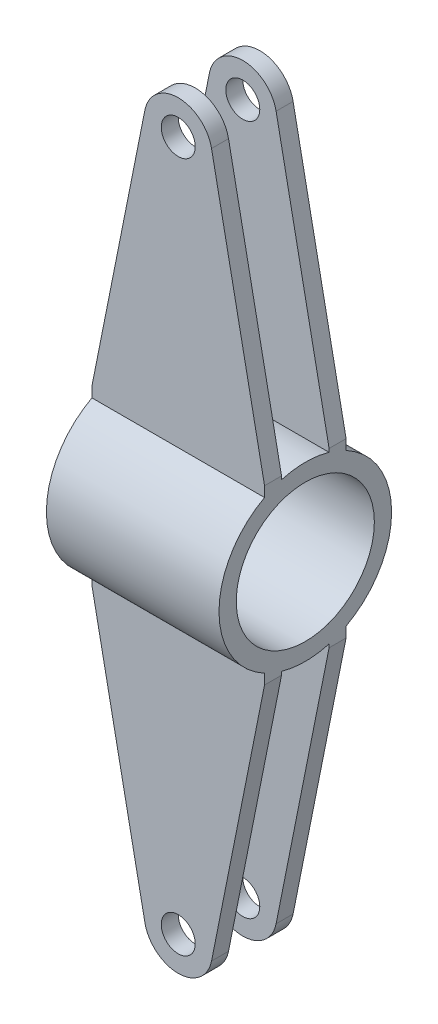
SolidWorks part; units mm, degrees
ref_plane "Front Plane" through (0, 0, 0) normal (0, 0, 1) x (1, 0, 0)
ref_plane "Top Plane" through (0, 0, 0) normal (0, 1, 0) x (1, 0, 0)
ref_plane "Right Plane" through (0, 0, 0) normal (1, 0, 0) x (0, 0, -1)
sketch "Sketch1" plane through (0, 0, 0) normal (0, 0, 1) x (1, 0, 0)
  line L0 (0, 101.6) -> (0, -101.6) construction
  point P4 (0, 0)
  dimension "D1" = 203.2
sketch "Sketch3" plane through (0, 0, 0) normal (1, 0, 0) x (0, 0, -1)
  circle A0 centre (0, 0) radius 25.4
  circle A1 centre (0, 0) radius 20.32
  dimension "D1" = 50.8
  dimension "D2" = 5.08
extrude "Boss-Extrude1" add sketch "Sketch3" along normal mid plane 50.8
sketch "Sketch4" plane through (0, 0, 0) normal (0, 0, 1) x (1, 0, 0)
  line L0 (-25.4, 25.4) -> (-9.8067, 103.5566)
  line L1 (25.4, 25.4) -> (9.8067, 103.5566)
  line L2 (-25.4, 25.4) -> (25.4, 25.4)
  line L3 (-25.4, -25.4) -> (-9.8067, -103.5566)
  line L4 (-25.4, 25.4) -> (-25.4, -25.4) construction
  line L5 (9.8067, -103.5566) -> (25.4, -25.4)
  line L6 (-25.4, -25.4) -> (25.4, -25.4)
  circle A0 centre (0, 101.6) radius 5
  arc A1 (9.8067, 103.5566) -> (-9.8067, 103.5566) centre (0, 101.6) ccw
  circle A2 centre (0, -101.6) radius 5
  arc A3 (-9.8067, -103.5566) -> (9.8067, -103.5566) centre (0, -101.6) ccw
  dimension "D1" = 20
  dimension "D2" = 10
  dimension "D3" = 20
  dimension "D4" = 10
extrude "Boss-Extrude3" add sketch "Sketch4" along normal blind 5 from offset 7 separate body
extrude "Boss-Extrude4" add sketch "Sketch4<2>" against normal blind 5 from offset 7 separate body offset against normal yes
sketch "Sketch4<2>" plane through (0, 0, 0) normal (0, 0, 1) x (1, 0, 0) same geometry as "Sketch4"
sketch "Sketch5" plane through (0, 0, 0) normal (1, 0, 0) x (0, 0, -1)
  line L0 (12, 25.4) -> (7, 25.4) construction
  line L1 (12, -25.4) -> (7, -25.4) construction
  line L2 (-12, -25.4) -> (-7, -25.4) construction
  line L3 (-12, 25.4) -> (-7, 25.4) construction
  line L4 (12, -25.4) -> (7, -25.4)
  line L5 (-12, -25.4) -> (-7, -25.4)
  line L6 (12, 25.4) -> (7, 25.4)
  line L7 (-12, 25.4) -> (-7, 25.4)
  line L8 (-12, 25.4) -> (-12, 22.3866)
  line L9 (-7, 25.4) -> (-7, 24.4164)
  line L10 (7, 25.4) -> (7, 24.4164)
  line L11 (12, 25.4) -> (12, 22.3866)
  line L12 (-12, -25.4) -> (-12, -22.3866)
  line L13 (-7, -25.4) -> (-7, -24.4164)
  line L14 (7, -25.4) -> (7, -24.4164)
  line L15 (12, -25.4) -> (12, -22.3866)
  circle A0 centre (0, 0) radius 25.4 construction
  arc A1 (-12, -22.3866) -> (-7, -24.4164) centre (0, 0) ccw
  arc A2 (12, 22.3866) -> (7, 24.4164) centre (0, 0) ccw
  arc A3 (7, -24.4164) -> (12, -22.3866) centre (0, 0) ccw
  arc A4 (-7, 24.4164) -> (-12, 22.3866) centre (0, 0) ccw
extrude "Boss-Extrude5" add sketch "Sketch5" along normal mid plane 50.8
